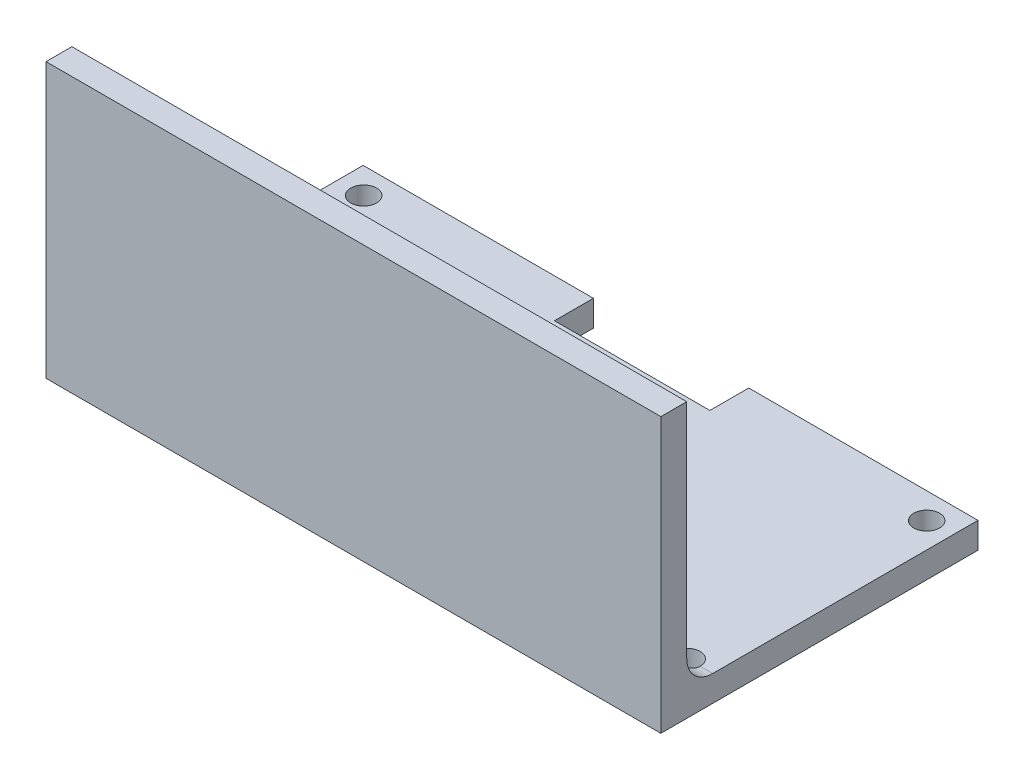
SolidWorks part; units mm, degrees
ref_plane "Front Plane" through (0, 0, 0) normal (0, 0, 1) x (1, 0, 0)
ref_plane "Top Plane" through (0, 0, 0) normal (0, 1, 0) x (1, 0, 0)
ref_plane "Right Plane" through (0, 0, 0) normal (1, 0, 0) x (0, 0, -1)
sketch "Sketch3" plane through (0, 0, 0) normal (0, 1, 0) x (1, 0, 0)
  line L1 (-79.8619, 6.7352) -> (-32.3619, 6.7352)
  line L2 (-79.8619, 6.7352) -> (-79.8619, -15.7648)
  line L3 (-79.8619, -15.7648) -> (-32.3619, -15.7648)
  line L4 (-32.3619, 6.7352) -> (-32.3619, -15.7648)
extrude "Boss-Extrude1" add sketch "Sketch3" along normal blind 2
sketch "Sketch52" plane through (0, 0, -0.0407) normal (0, -1, 0) x (1, 0, 0)
  circle A0 centre (-77.8239, -4.6945) radius 1
  circle A1 centre (-77.8239, -4.6945) radius 0.0477
sketch "Sketch53" plane through (0.0044, 0, 0) normal (0, -1, 0) x (-1, 0, 0)
  circle A0 centre (34.3289, 4.7354) radius 0.9952
sketch "Sketch56" plane through (0, 0, 0) normal (0, -1, 0) x (-1, 0, 0)
  circle A0 centre (34.3264, -13.7651) radius 0.9976
extrude "Cut-Extrude1" cut sketch "Sketch56" against normal blind 10
extrude "Cut-Extrude2" cut sketch "Sketch53" against normal blind 10 contours A0 | A0 region at (-34.3245, 0, -4.7354)
extrude "Cut-Extrude3" cut sketch "Sketch52" against normal blind 10 contours A0
sketch "Sketch57" plane through (0, 0, 0) normal (0, -1, 0) x (1, 0, 0)
  line L0 (-77.8264, 13.7648) -> (-77.8264, 15.7648) construction
  line L1 (-79.8619, 15.7648) -> (-32.3619, 15.7648) construction
  circle A0 centre (-77.8264, 13.7648) radius 1
  point P2 (0, 0)
extrude "Cut-Extrude4" cut sketch "Sketch57" against normal blind 10 contours A0
sketch "Sketch74" plane through (0, 2, 0) normal (0, 1, 0) x (1, 0, 0)
  line L1 (-62.0739, 6.7352) -> (-50.0697, 6.7352)
  line L2 (-79.8619, 6.7352) -> (-32.3619, 6.7352) construction
  line L4 (-62.0739, 4.7352) -> (-62.0739, 6.7352)
  line L5 (-62.0739, 6.7352) -> (-50.0697, 6.7352)
  line L6 (-50.0697, 4.7352) -> (-50.0697, 6.7352)
  line L7 (-62.0739, 4.7352) -> (-50.0697, 6.7352) construction
  line L8 (-62.0739, 6.7352) -> (-50.0697, 4.7352) construction
  line L9 (-62.0739, 6.7352) -> (-62.0739, 3.7303)
  line L10 (-62.0739, 3.7303) -> (-50.0697, 3.7303)
  line L11 (-50.0697, 6.7352) -> (-50.0697, 3.7303)
  line L12 (-62.0739, 6.7352) -> (-50.0697, 3.7303) construction
  line L13 (-62.0739, 3.7303) -> (-50.0697, 6.7352) construction
  point P3 (-56.0718, 5.2328)
  point P4 (0, 0)
  point P5 (0, 0)
  point P6 (0, 0)
sketch "Sketch77" plane through (0, 2, 0) normal (0, 1, 0) x (1, 0, 0)
extrude "Cut-Extrude6" cut sketch "Sketch74" against normal blind 10 contours L9 L1 L11 L10
sketch "Sketch79" plane through (0, 0, 0) normal (0, 1, 0) x (1, 0, 0)
  line L0 (-79.8619, -15.7648) -> (-32.3619, -15.7648) construction
  line L1 (-79.8619, -15.7648) -> (-32.3619, -15.7648)
  line L2 (-79.8619, -15.7648) -> (-79.8619, -17.7648)
  line L3 (-79.8619, -17.7648) -> (-32.3619, -17.7648)
  line L4 (-32.3619, -15.7648) -> (-32.3619, -17.7648)
extrude "Boss-Extrude2" add sketch "Sketch79" along normal blind 21.1901
fillet "Fillet6" radius 2 1 edges at (-56.1119, 2, 15.7648) type face fillet first side face at (-56.1119, 11.595, 15.7648) second side face at (-56.0919, 2, -0.359)
